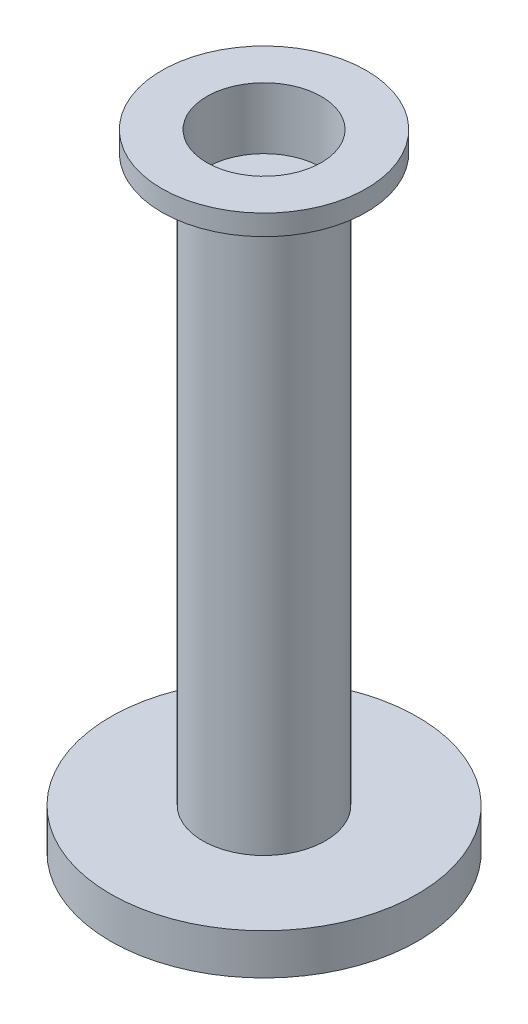
SolidWorks part; units mm, degrees
material "1023 Carbon Steel Sheet (SS)"
ref_plane "Front Plane" through (0, 0, 0) normal (0, 0, 1) x (1, 0, 0)
ref_plane "Top Plane" through (0, 0, 0) normal (0, 1, 0) x (1, 0, 0)
ref_plane "Right Plane" through (0, 0, 0) normal (1, 0, 0) x (0, 0, -1)
sketch "Sketch1" plane through (0, 0, 0) normal (0, 1, 0) x (1, 0, 0)
  circle A0 centre (0, 0) radius 3.75
  dimension "D1" = 7.5
extrude "Boss-Extrude1" add sketch "Sketch1" along normal blind 1
sketch "Sketch2" plane through (0, 1, 0) normal (0, 1, 0) x (1, 0, 0)
  circle A0 centre (0, 0) radius 1.5
  dimension "D1" = 3
extrude "Boss-Extrude2" add sketch "Sketch2" along normal blind 13.8
sketch "Sketch3" plane through (0, 14.8, 0) normal (0, 1, 0) x (1, 0, 0)
  circle A0 centre (0, 0) radius 2.5
  dimension "D1" = 5
extrude "Boss-Extrude3" add sketch "Sketch3" along normal blind 0.5
sketch "Sketch4" plane through (0, 15.3, 0) normal (0, 1, 0) x (1, 0, 0)
  circle A0 centre (0, 0) radius 1.4
  dimension "D1" = 2.8
extrude "Cut-Extrude2" cut sketch "Sketch4" against normal blind 1.5
